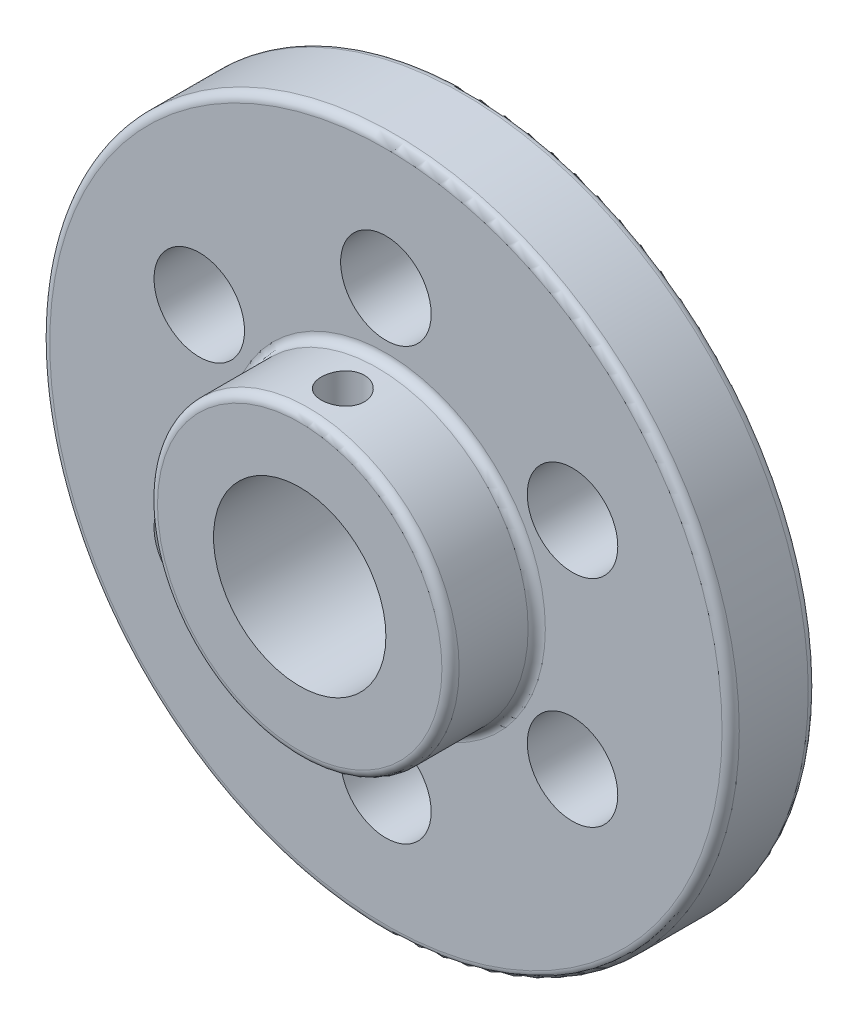
SolidWorks part; units mm, degrees
material "Gray Cast Iron"
ref_plane "Front Plane" through (0, 0, 0) normal (0, 0, 1) x (1, 0, 0)
ref_plane "Top Plane" through (0, 0, 0) normal (0, 1, 0) x (1, 0, 0)
ref_plane "Right Plane" through (0, 0, 0) normal (1, 0, 0) x (0, 0, -1)
sketch "Sketch1" plane through (0, 0, 0) normal (0, 0, 1) x (1, 0, 0)
  circle A0 centre (0, 0) radius 40
  circle A1 centre (0, 0) radius 10
  dimension "D1" = 80
  dimension "D2" = 20
extrude "Boss-Extrude1" add sketch "Sketch1" along normal blind 10
sketch "Sketch2" plane through (0, 0, 10) normal (0, 0, 1) x (1, 0, 0)
  circle A0 centre (0, 0) radius 25 construction
  circle A1 centre (0, 25) radius 5 construction
  dimension "D1" = 50
  dimension "D2" = 10
hole_wizard "M12x1.5 Tapped Hole1" positions "Sketch3" profile "Sketch4" tap size "M12x1.5" standard "ANSI Metric" end condition through all
sketch "Sketch3" plane through (0, 0, 10) normal (0, 0, 1) x (1, 0, 0)
  point P0 (0, 25)
sketch "Sketch4" plane through (0, 25, 10) normal (1, 0, 0) x (0, -1, 0)
  line L0 (0, 0) -> (0, 10)
  line L1 (0, 10) -> (5.25, 10)
  line L2 (5.25, 10) -> (5.25, 0)
  line L5 (5.25, 0) -> (0, 0)
  line L11 (0, -6.35) -> (0, 107.95) construction
  dimension "Thru Tap Drill Dia." = 10.5
  dimension "Thru Tap Drill Depth" = 10
cosmetic thread "Hole Thread1" parameters "D2"=12
pattern_circular "CirPattern1" count 6 over 360 about axis through (0, 0, 10) along (0, 0, 1) of "M12x1.5 Tapped Hole1"
cosmetic thread "Hole Thread2" parameters "D2"=12
cosmetic thread "Hole Thread3" parameters "D2"=12
cosmetic thread "Hole Thread4" parameters "D2"=12
cosmetic thread "Hole Thread5" parameters "D2"=12
cosmetic thread "Hole Thread6" parameters "D2"=12
sketch "Sketch5" plane through (0, 0, 10) normal (0, 0, 1) x (1, 0, 0)
  circle A0 centre (0, 0) radius 17.5
  circle A1 centre (0, 0) radius 10 construction
  circle A2 centre (0, 0) radius 10
  dimension "D1" = 35
extrude "Boss-Extrude2" add sketch "Sketch5" along normal blind 10
ref_plane "Plane1" through (0, 17.5, 0) normal (0, 1, 0) x (1, 0, 0)
sketch "Sketch6" plane through (0, 17.5, 0) normal (0, 1, 0) x (1, 0, 0)
  line L0 (-17.5, -20) -> (17.5, -20) construction
  line L1 (17.5, -20) -> (17.5, -10) construction
  line L2 (-17.5, -10) -> (17.5, -10) construction
  line L3 (-17.5, -10) -> (-17.5, -20) construction
  line L4 (-17.5, -20) -> (17.5, -20) construction
  line L5 (17.5, -20) -> (17.5, -10) construction
  line L6 (-17.5, -10) -> (17.5, -10) construction
  line L7 (-17.5, -10) -> (-17.5, -20) construction
  line L9 (-17.5, -10) -> (17.5, -10) construction
  line L10 (-17.5, -10) -> (-17.5, -20)
  line L11 (-17.5, -20) -> (17.5, -20)
  line L12 (17.5, -10) -> (17.5, -20)
  line L13 (-17.5, -10) -> (17.5, -20) construction
  line L14 (-17.5, -20) -> (17.5, -10) construction
  circle A0 centre (0, -15) radius 2.5
  point P5 (0, -15)
  dimension "D1" = 5
hole_wizard "M6x1.0 Tapped Hole1" positions "Sketch7" profile "Sketch8" tap size "M6x1.0" standard "ANSI Metric" end condition up to next
sketch "Sketch7" plane through (0, 17.5, 0) normal (0, 1, 0) x (1, 0, 0)
  point P0 (0, -15)
sketch "Sketch8" plane through (0, 17.5, 15) normal (1, 0, 0) x (0, 0, 1)
  line L0 (0, 0) -> (0, 7.5)
  line L1 (0, 7.5) -> (2.5, 7.5)
  line L2 (2.5, 7.5) -> (2.5, 0)
  line L5 (2.5, 0) -> (0, 0)
  line L11 (0, -6.35) -> (0, 107.95) construction
  dimension "Thru Tap Drill Dia." = 5
  dimension "Thru Tap Drill Depth" = 7.5
cosmetic thread "Hole Thread7" parameters "D2"=6
fillet "Fillet1" radius 1 4 edges at (17.5, 0, 20) (17.5, 0, 10) (40, 0, 0) (40, 0, 10)
